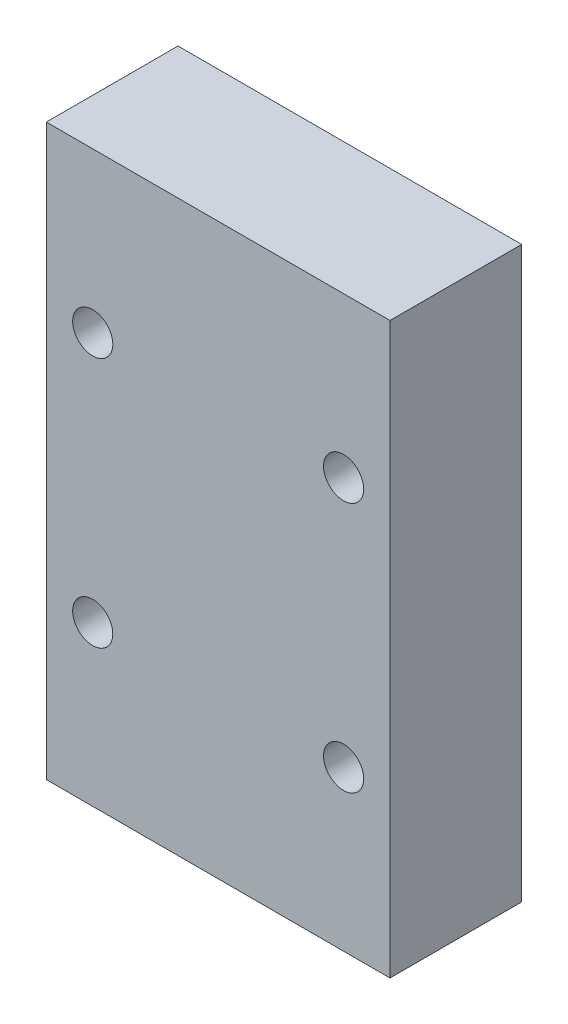
SolidWorks part; units mm, degrees
ref_plane "Front Plane" through (0, 0, 0) normal (0, 0, 1) x (1, 0, 0)
ref_plane "Top Plane" through (0, 0, 0) normal (0, 1, 0) x (1, 0, 0)
ref_plane "Right Plane" through (0, 0, 0) normal (1, 0, 0) x (0, 0, -1)
sketch "Sketch1" plane through (0, 0, 0) normal (0, 0, 1) x (1, 0, 0)
  line L0 (-94.8117, 4.8324) -> (-108.5117, 4.8324) construction
  line L1 (-81.1117, -17.8676) -> (-108.5117, -17.8676)
  line L2 (-81.1117, -17.8676) -> (-81.1117, 27.5324)
  line L3 (-81.1117, 27.5324) -> (-108.5117, 27.5324)
  line L4 (-108.5117, -17.8676) -> (-108.5117, 27.5324)
  line L5 (-81.1117, -17.8676) -> (-108.5117, 27.5324) construction
  line L6 (-81.1117, 27.5324) -> (-108.5117, -17.8676) construction
  line L7 (-94.8117, 4.8324) -> (-94.8117, -17.8676) construction
  line L10 (-94.8117, 462.9351) -> (-94.8117, -687.0649) construction
  line L11 (-109.8117, 12.4297) -> (-109.8117, -2.7648) construction
  line L12 (-109.8117, 12.4297) -> (-109.8117, -2.7648) construction
  line L13 (-108.5117, 4.8324) -> (-109.8117, 4.8324) construction
  circle A0 centre (-104.8117, -5.1676) radius 1.6
  circle A1 centre (-104.8117, 14.8324) radius 1.6
  circle A2 centre (-84.8117, 14.8324) radius 1.6
  circle A3 centre (-84.8117, -5.1676) radius 1.6
  point P0 (-94.8117, 4.8324)
  dimension "D5" = 3.2
  dimension "D1" = 27.4
  dimension "D2" = 45.4
  dimension "D3" = 10
  dimension "D4" = 10
extrude "Boss-Extrude1" add sketch "Sketch1" along normal blind 5 and the other way blind 5.5
